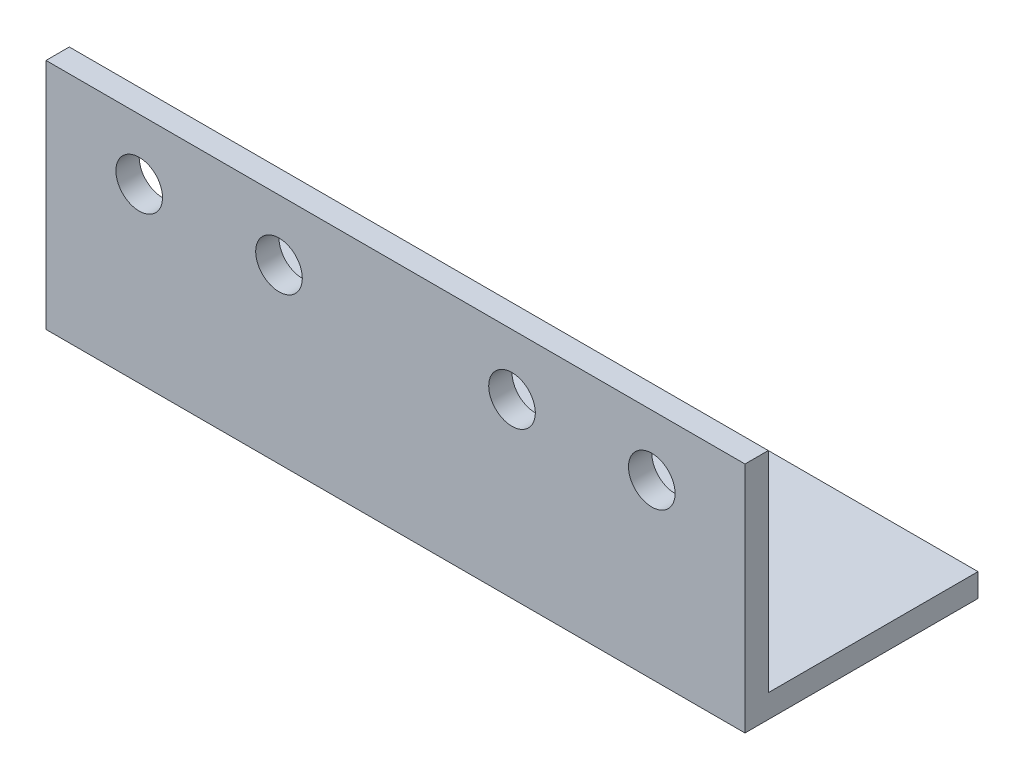
SolidWorks part; units mm, degrees
ref_plane "Спереди" through (0, 0, 0) normal (0, 0, 1) x (1, 0, 0)
ref_plane "Сверху" through (0, 0, 0) normal (0, 1, 0) x (1, 0, 0)
ref_plane "Справа" through (0, 0, 0) normal (1, 0, 0) x (0, 0, -1)
sketch "Эскиз1" plane through (0, 0, 0) normal (1, 0, 0) x (0, 0, -1)
  line L0 (0, 0) -> (0, 50)
  line L1 (0, 0) -> (50, 0)
extrude "Вытянуть-Тонкостенный1" add sketch "Эскиз1" along normal blind 150 thin thin type one direction reverse wall 5
sketch "Эскиз2" plane through (0, 0, 0) normal (0, 0, 1) x (1, 0, 0)
  line L0 (75, 57.1198) -> (75, 24.9932) construction
  circle A0 centre (20, 37) radius 5
  circle A1 centre (50, 37) radius 5
  circle A2 centre (100, 37) radius 5
  circle A3 centre (130, 37) radius 5
  dimension "D1" = 2
extrude "Вырез-Вытянуть1" cut sketch "Эскиз2" against normal through all
sketch "Эскиз3" plane through (0, 0, 0) normal (0, -1, 0) x (1, 0, 0)
  line L0 (75, -55.6806) -> (75, -1.3862) construction
  circle A0 centre (130, -18) radius 5
  circle A1 centre (100, -18) radius 5
  circle A2 centre (50, -18) radius 5
  circle A3 centre (20, -18) radius 5
  dimension "D1" = 2
extrude "Вырез-Вытянуть2" cut sketch "Эскиз3" against normal through all
